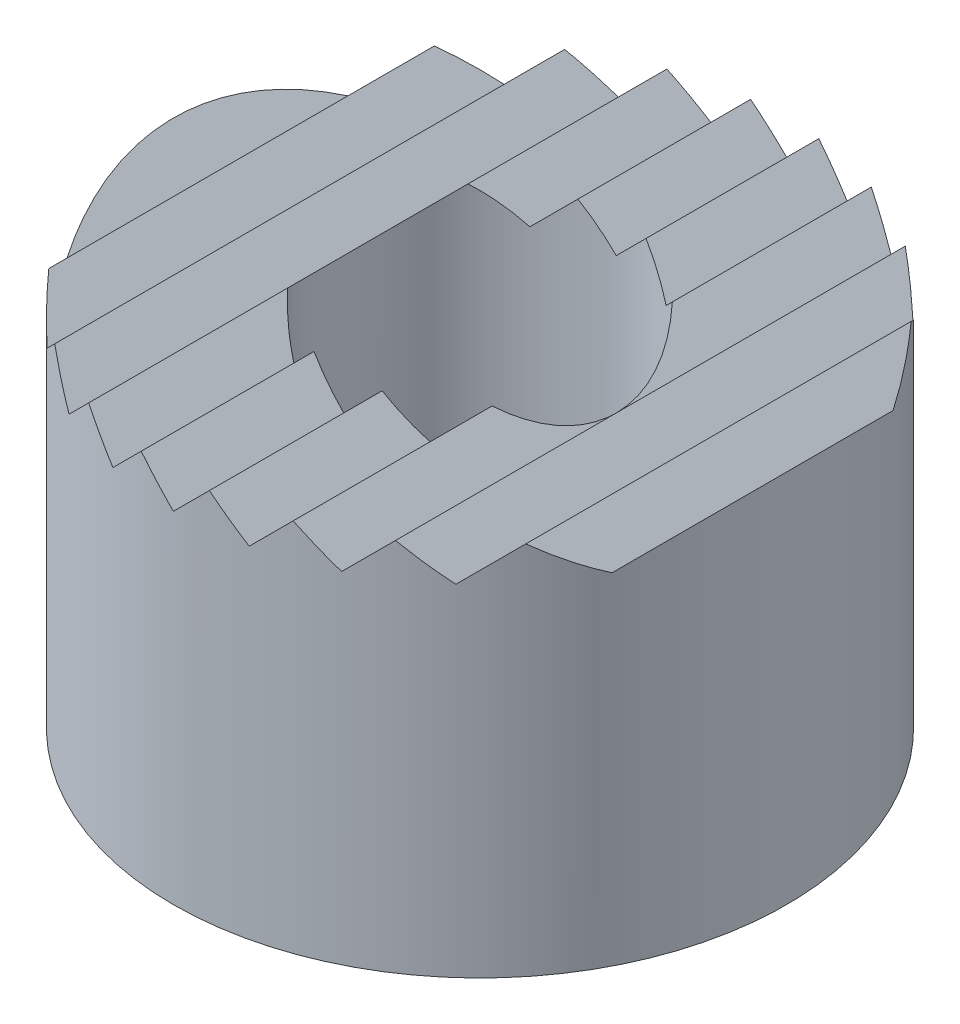
SolidWorks part; units mm, degrees
ref_plane "前视基准面" through (0, 0, 0) normal (0, 0, 1) x (1, 0, 0)
ref_plane "上视基准面" through (0, 0, 0) normal (0, 1, 0) x (1, 0, 0)
ref_plane "右视基准面" through (0, 0, 0) normal (1, 0, 0) x (0, 0, -1)
sketch "草图1" plane through (0, 0, 0) normal (0, 1, 0) x (1, 0, 0)
  circle A0 centre (0, 0) radius 1.6
  circle A1 centre (0, 0) radius 3.6
  dimension "D1" = 3.2
  dimension "D2" = 2
extrude "凸台-拉伸1" add sketch "草图1" along normal blind 4.4
sketch "草图2" plane through (0, 0, 0) normal (0, 0, 1) x (1, 0, 0)
  line L0 (-3.6, 4.4) -> (-3.2, 4)
  line L1 (-3.2, 4) -> (-2.8, 4.4)
  line L2 (3.6, 4.4) -> (-3.6, 4.4) construction
  line L20 (-2.8, 4.4) -> (-3.6, 4.4)
  line L21 (-2, 4.4) -> (-2.8, 4.4)
  line L22 (-2.8, 4.4) -> (-2.4, 4)
  line L23 (-2.4, 4) -> (-2, 4.4)
  line L24 (-1.2, 4.4) -> (-2, 4.4)
  line L25 (-2, 4.4) -> (-1.6, 4)
  line L26 (-1.6, 4) -> (-1.2, 4.4)
  line L27 (-0.4, 4.4) -> (-1.2, 4.4)
  line L28 (-1.2, 4.4) -> (-0.8, 4)
  line L29 (-0.8, 4) -> (-0.4, 4.4)
  line L30 (0.4, 4.4) -> (-0.4, 4.4)
  line L31 (-0.4, 4.4) -> (0, 4)
  line L32 (0, 4) -> (0.4, 4.4)
  line L33 (1.2, 4.4) -> (0.4, 4.4)
  line L34 (0.4, 4.4) -> (0.8, 4)
  line L35 (0.8, 4) -> (1.2, 4.4)
  line L36 (2, 4.4) -> (1.2, 4.4)
  line L37 (1.2, 4.4) -> (1.6, 4)
  line L38 (1.6, 4) -> (2, 4.4)
  line L39 (2.8, 4.4) -> (2, 4.4)
  line L40 (2, 4.4) -> (2.4, 4)
  line L41 (2.4, 4) -> (2.8, 4.4)
  line L42 (3.6, 4.4) -> (2.8, 4.4)
  line L43 (2.8, 4.4) -> (3.2, 4)
  line L44 (3.2, 4) -> (3.6, 4.4)
  dimension "D1" = 45
  dimension "D2" = 0.8
  dimension "D3" = 9
extrude "切除-拉伸1" cut sketch "草图2" against normal blind 10 and the other way blind 10 contours L23 L21 L22 | L20 L0 L1 | L26 L24 L25 | L28 L29 L27 | L31 L32 L30 | L34 L35 L33 | L37 L38 L36 | L40 L41 L39 | L43 L44 L42
